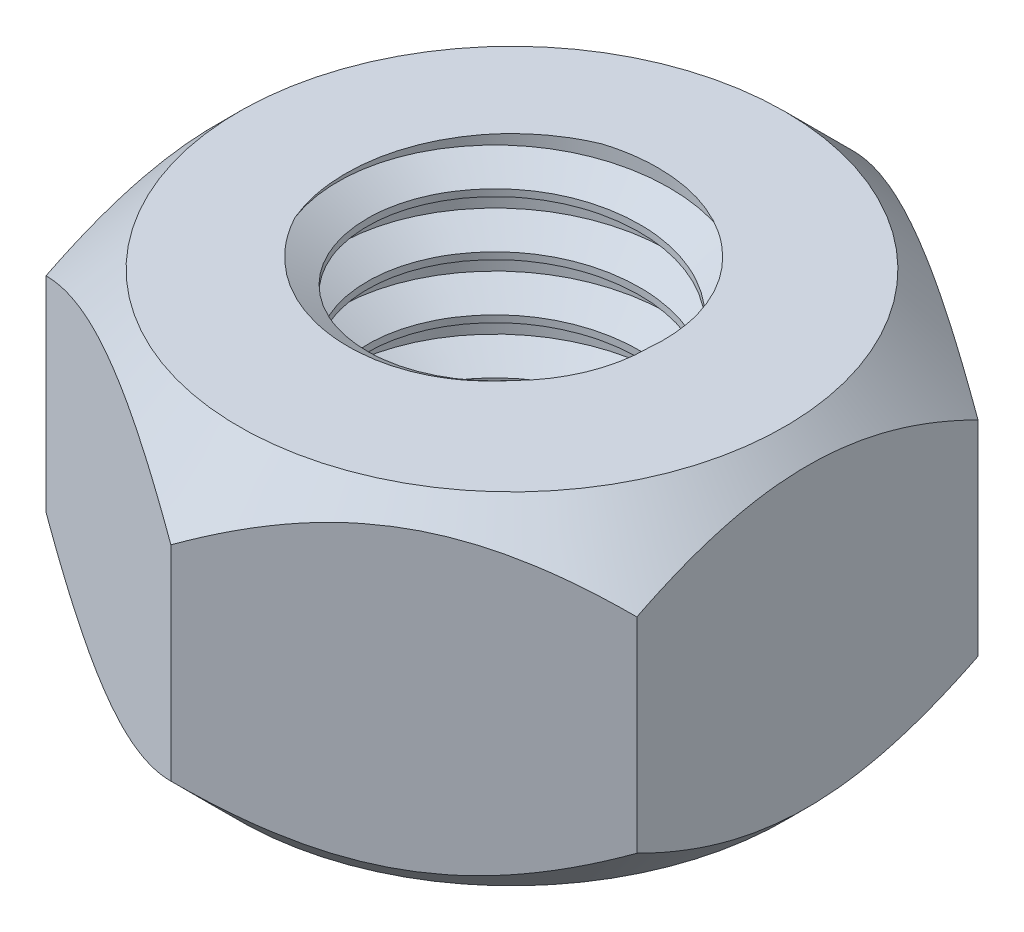
SolidWorks part; units mm, degrees
ref_plane "Front Plane" through (0, 0, 0) normal (0, 0, 1) x (1, 0, 0)
ref_plane "Top Plane" through (0, 0, 0) normal (0, 1, 0) x (1, 0, 0)
ref_plane "Right Plane" through (0, 0, 0) normal (1, 0, 0) x (0, 0, -1)
sketch "Sketch1" plane through (0, 0, 0) normal (0, 1, 0) x (1, 0, 0)
  line L1 (0, 5) -> (-4.3301, 2.5)
  line L2 (-4.3301, 2.5) -> (-4.3301, -2.5)
  line L3 (-4.3301, -2.5) -> (0, -5)
  line L4 (0, -5) -> (4.3301, -2.5)
  line L5 (4.3301, -2.5) -> (4.3301, 2.5)
  line L6 (4.3301, 2.5) -> (0, 5)
  circle A0 centre (0, 0) radius 4.3301 construction
  dimension "D1" = 10
extrude "Boss-Extrude1" add sketch "Sketch1" along normal mid plane 5
sketch "Sketch2" plane through (0, 2.5, 0) normal (0, 1, 0) x (1, 0, 0)
  circle A0 centre (0, 0) radius 2
  dimension "D1" = 4
extrude "Cut-Extrude1" cut sketch "Sketch2" against normal through all
thread "Thread1" pitch 0.8 method cut trim with start face yes trim with end face yes profile "Thread Profile1" start angle 0, offset 2, length 10, pitch 0.8, diameter 4
ref_plane "Plane1" through (-2, 4.5, 0) normal (0, 0, -1) x (1, 0, 0)
sketch "Thread Profile1" plane through (-2, 4.5, 0) normal (0, 0, -1) x (1, 0, 0)
  line L0 (0, 0) -> (0, 0.8) construction
  line L11 (0, 0) -> (0, 0.7)
  line L12 (0, 0.7) -> (-0.433, 0.45)
  line L13 (-0.433, 0.45) -> (-0.433, 0.25)
  line L15 (-0.433, 0.25) -> (0, 0)
  line L17 (-0.433, 0.35) -> (0, 0.35) construction
  point P2 (0, 0)
  dimension "Pitch" = 0.8
  dimension "Profile_Angle" = 60
  dimension "Profile_Land" = 0.2
  dimension "Profile_Height" = 0.433
sketch "Sketch4" plane through (0, 0, 0) normal (1, 0, 0) x (0, 0, -1)
  line L0 (5, 2.5) -> (4, 2.5)
  line L1 (2.5, 2.5) -> (5, 2.5) construction
  line L2 (4, 2.5) -> (5, 1.5)
  line L3 (5, 2.5) -> (5, -2.5) construction
  line L4 (5, 1.5) -> (5, 2.5)
  line L5 (0, 0) -> (0, 3.0999) construction
  dimension "D1" = 45
  dimension "D2" = 1
revolve "Cut-Revolve2" cut sketch "Sketch4" angle 360 about L5
mirror "Mirror1" about plane through (0, 0, 0) normal (0, 1, 0) of "Cut-Revolve2"
